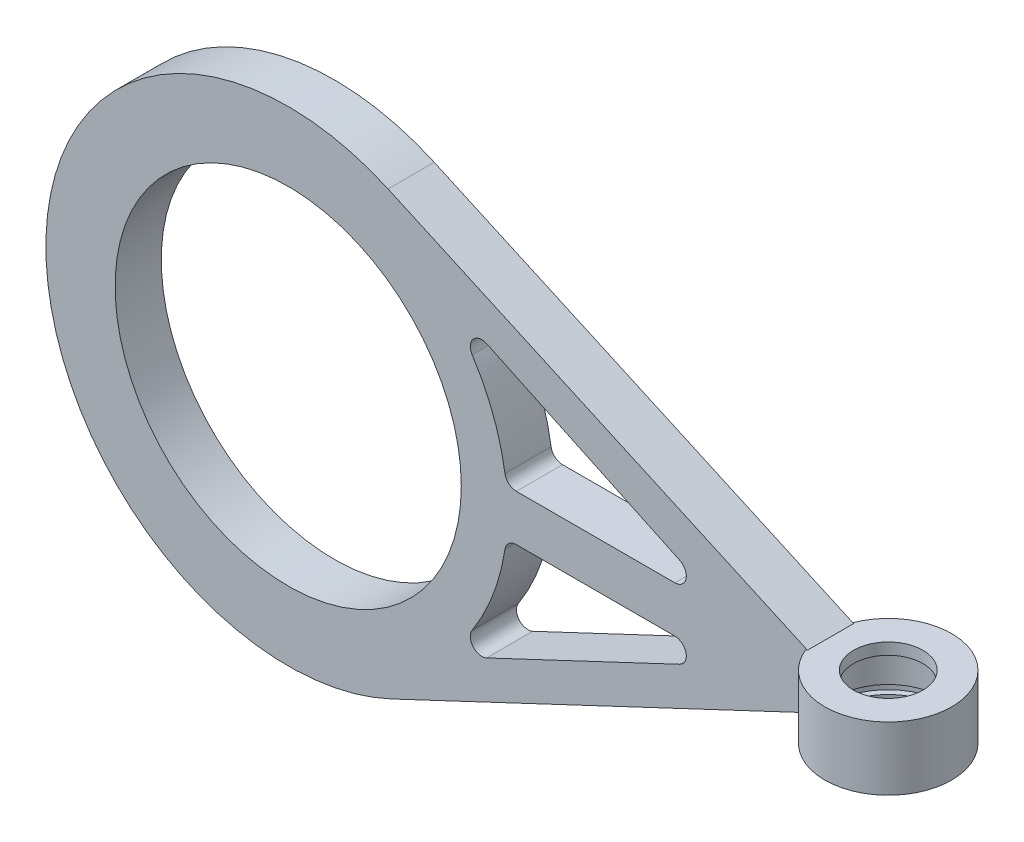
SolidWorks part; units mm, degrees
ref_plane "前视基准面" through (0, 0, 0) normal (0, 0, 1) x (1, 0, 0)
ref_plane "上视基准面" through (0, 0, 0) normal (0, 1, 0) x (1, 0, 0)
ref_plane "右视基准面" through (0, 0, 0) normal (1, 0, 0) x (0, 0, -1)
other "Configuration Table"
sketch "草图1" plane through (0, 0, 0) normal (0, 0, 1) x (1, 0, 0)
  circle A0 centre (0, 0) radius 42
  dimension "D1" = 84
extrude "凸台-拉伸1" add sketch "草图1" along normal blind 3
sketch "草图2" plane through (0, 0, 3) normal (0, 0, 1) x (1, 0, 0)
  line L0 (0, 0) -> (150.9371, 0) construction
  line L1 (100, 22.7173) -> (100, -21.6499) construction
  line L3 (89, 5.375) -> (100, 5.375)
  line L4 (89, 5.375) -> (89, -5.625)
  line L8 (89, -5.625) -> (100, -5.625)
  line L9 (100, 5.375) -> (100, -5.625)
  dimension "D2" = 11
  dimension "D1" = 100
  dimension "D3" = 5.375
  dimension "D4" = 11
revolve "旋转1" add sketch "草图2" angle 360 about L1
sketch "草图3" plane through (0, 0, 3) normal (0, 0, 1) x (1, 0, 0)
  line L0 (17.3147, 38.2649) -> (90, 5.375)
  line L1 (17.9116, -37.9891) -> (90, -4)
  line L4 (90, 5.375) -> (90, -4)
  circle A1 centre (0, 0) radius 42
  arc A2 (17.3147, 38.2649) -> (17.9116, -37.9891) centre (0, 0) ccw
  dimension "D2" = 90
  dimension "D3" = 5.375
  dimension "D4" = 4
  dimension "D1" = 0
extrude "凸台-拉伸2" add sketch "草图3" along normal mid plane 8
sketch "草图4" plane through (0, -5.625, 0) normal (0, -1, 0) x (1, 0, 0)
  circle A0 centre (100, 3) radius 6
  dimension "D1" = 12
extrude "切除-拉伸1" cut sketch "草图4" against normal blind 25
sketch "草图5" plane through (0, -5.625, 0) normal (0, -1, 0) x (1, 0, 0)
  circle A0 centre (100, 3) radius 9
  dimension "D1" = 18
extrude "切除-拉伸2" cut sketch "草图5" against normal offset from surface (9 mm away) 2 up to face at (100, 5.375, 9)
sketch "草图6" plane through (0, 3.375, 0) normal (0, -1, 0) x (1, 0, 0)
  circle A0 centre (100, 3) radius 10
  circle A1 centre (100, 3) radius 9 construction
  circle A2 centre (100, 3) radius 9 construction
  circle A3 centre (100, 3) radius 9
  circle M1 centre (100, 3) radius 9
  dimension "D1" = 1
extrude "切除-拉伸3" cut sketch "草图6" along normal blind 1.5 from offset 6.5 contours A0 M1 region at (90.2828, 3.375, 3)
sketch "草图7" plane through (0, 0, 7) normal (0, 0, 1) x (1, 0, 0)
  line L0 (26.3566, -27.3739) -> (75.9309, -4)
  line L1 (0, 0) -> (55.8434, 0) construction
  line L2 (17.9116, -37.9891) -> (89.753, -4.1164) construction
  line L4 (37.7889, -4) -> (75.9309, -4)
  line L5 (37.7889, 4) -> (75.9309, 4)
  line L6 (26.3566, 27.3739) -> (75.9309, 4)
  circle A0 centre (0, 0) radius 30
  arc A1 (26.3566, -27.3739) -> (37.7889, -4) centre (0, 0) ccw
  arc A2 (26.3566, 27.3739) -> (37.7889, 4) centre (0, 0) cw
  dimension "D1" = 60
  dimension "D3" = 8
  dimension "D2" = 6
  dimension "D4" = 4
extrude "切除-拉伸4" cut sketch "草图7" against normal blind 30
fillet "圆角1" radius 2 6 edges at (37.7889, 4, 3) (26.3566, 27.3739, 3) (75.9309, 4, 3) (75.9309, -4, 3) (37.7889, -4, 3) (26.3566, -27.3739, 3)
